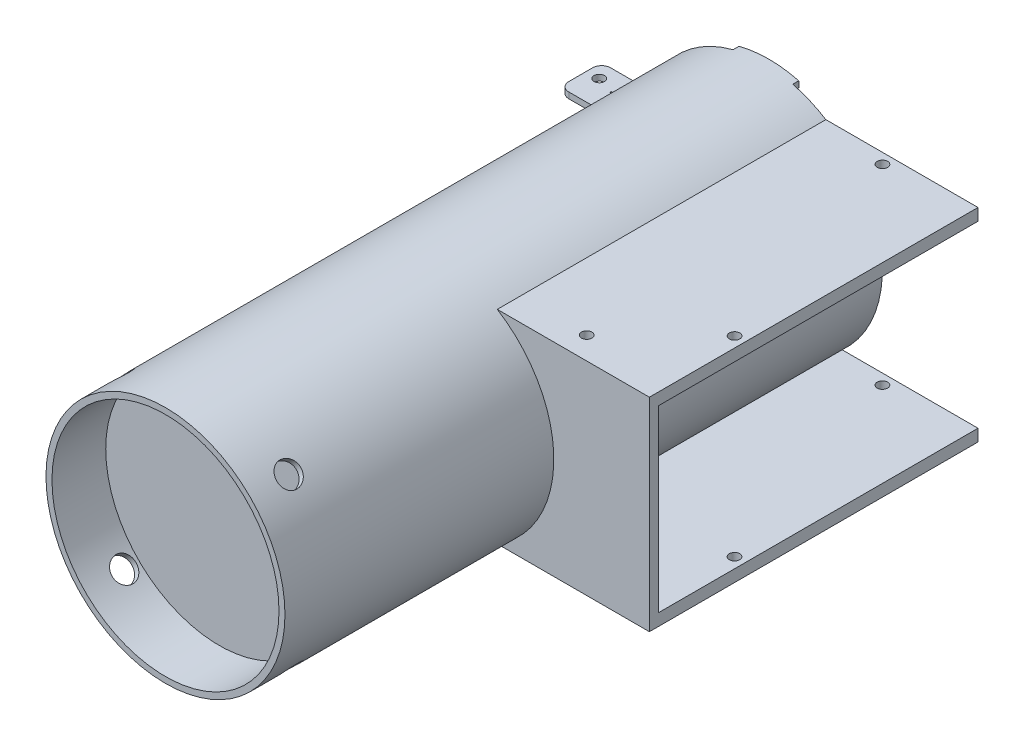
SolidWorks part; units mm, degrees
material "Acrylic (Medium-high impact)"
ref_plane "Front Plane" through (0, 0, 0) normal (0, 0, 1) x (1, 0, 0)
ref_plane "Top Plane" through (0, 0, 0) normal (0, 1, 0) x (1, 0, 0)
ref_plane "Right Plane" through (0, 0, 0) normal (1, 0, 0) x (0, 0, -1)
ref_axis "Axis1" through (0, 0, 106.8) along (0, 0, 1)
sketch "Sketch1" plane through (0, 0, 0) normal (0, 0, 1) x (1, 0, 0)
  circle A0 centre (0, 0) radius 38
  circle A1 centre (0, 0) radius 40
  dimension "D1" = 76
  dimension "D2" = 2
extrude "Boss-Extrude1" add sketch "Sketch1" along normal blind 200
ref_plane "Plane1" through (0, 0, 180) normal (0, 0, 1) x (1, 0, 0)
sketch "Sketch2" plane through (0, 0, 180) normal (0, 0, 1) x (1, 0, 0)
  circle A0 centre (0, 0) radius 40 construction
  circle A1 centre (0, 0) radius 40
extrude "Boss-Extrude2" add sketch "Sketch2" along normal blind 2
sketch "Sketch3" plane through (0, 0, 0) normal (0, 0, -1) x (-1, 0, 0)
  line L0 (-21.0713, -34) -> (-72, -34)
  line L1 (-72, -34) -> (-72, -30)
  line L2 (-72, -30) -> (-26.4575, -30)
  line L3 (-21.0713, 34) -> (-72, 34)
  line L4 (-72, 30) -> (-26.4575, 30)
  line L5 (-72, 34) -> (-72, 30)
  line L6 (-40, -15.2942) -> (-40, 13.2229) construction
  line L8 (0, 0) -> (-59.0266, 0) construction
  circle A1 centre (0, 0) radius 40 construction
  arc A2 (-21.0713, 34) -> (-26.4575, 30) centre (0, 0) ccw
  arc A3 (-26.4575, -30) -> (-21.0713, -34) centre (0, 0) ccw
  dimension "D1" = 60
  dimension "D2" = 4
  dimension "D3" = 32
extrude "Boss-Extrude3" add sketch "Sketch3" against normal blind 107
sketch "Sketch4" plane through (0, 0, 107) normal (0, 0, 1) x (1, 0, 0)
  line L2 (72, -34) -> (21.0713, -34) construction
  line L3 (21.0713, 34) -> (72, 34) construction
  line L4 (72, -34) -> (21.0713, -34)
  line L5 (21.0713, 34) -> (72, 34)
  line L6 (72, -34) -> (72, 34)
  circle A0 centre (0, 0) radius 40 construction
  arc A2 (21.0713, -34) -> (21.0713, 34) centre (0, 0) ccw
extrude "Boss-Extrude4" add sketch "Sketch4" along normal blind 3
sketch "Sketch5" plane through (0, 34, 0) normal (0, 1, 0) x (1, 0, 0)
  circle A5 centre (43.5, -102.5) radius 1.75 construction
  circle A6 centre (43.5, -102.5) radius 1.75
  circle A7 centre (43.5, -3.5) radius 1.75 construction
  circle A8 centre (43.5, -3.5) radius 1.75
  circle A9 centre (68.5, -78) radius 1.75 construction
  circle A10 centre (68.5, -78) radius 1.75
extrude "Cut-Extrude1" cut sketch "Sketch5" against normal through all
ref_plane "Plane2" through (0, 0, 0) normal (-0.7071, 0.7071, 0) x (0, 0, 1)
sketch "Sketch6" plane through (0, 0, 0) normal (-0.7071, 0.7071, 0) x (0, 0, 1)
  line L0 (200, -40) -> (200, 40) construction
  line L1 (200, -40) -> (200, 40) construction
  circle A0 centre (187, 0) radius 4
  dimension "D1" = 8
  dimension "D2" = 13
extrude "Cut-Extrude2" cut sketch "Sketch6" against normal up to next and the other way up to next
pattern_circular "CirPattern1" count 2 every 90 about axis through (0, 0, 106.8) along (0, 0, 1) of "Cut-Extrude2"
ref_plane "Plane3" through (-54, 0, 0) normal (1, 0, 0) x (0, 0, -1)
sketch "Sketch7" plane through (-54, 0, 0) normal (1, 0, 0) x (0, 0, -1)
  line L0 (0, 0) -> (-33.0452, 0) construction
  line L1 (-14, -11) -> (0, -11)
  line L2 (-14, -11) -> (-14, -13)
  line L3 (-14, -13) -> (0, -13)
  line L4 (0, -11) -> (0, -13)
  line L5 (0, -40) -> (0, 40) construction
  line L6 (0, 11) -> (0, 13)
  line L7 (-14, 13) -> (0, 13)
  line L8 (-14, 11) -> (-14, 13)
  line L9 (-14, 11) -> (0, 11)
  dimension "D1" = 2
  dimension "D2" = 14
  dimension "D3" = 22
extrude "Boss-Extrude5" add sketch "Sketch7" along normal up to surface (15.5422 mm away) up to face at (25.3934, 30.9059, 187.8976)
sketch "Sketch8" plane through (0, -13, 0) normal (0, -1, 0) x (1, 0, 0)
  line L6 (-37.8286, 14) -> (-37.8286, 0) construction
  line L7 (-37.8286, 0) -> (-54, 0) construction
  circle A0 centre (-49.7703, 5.0088) radius 1.75
  dimension "D3" = 3.5
  dimension "D1" = 11.9417
  dimension "D2" = 5.0088
extrude "Cut-Extrude3" cut sketch "Sketch8" against normal up to surface (26 mm away) up to face at (-45.9143, 13, 7)
fillet "Fillet1" radius 3 4 edges at (-54, 12, 0) (-54, -12, 0) (-54, -12, 14) (-54, 12, 14)
sketch "Sketch9" plane through (0, 11, 0) normal (0, -1, 0) x (1, 0, 0)
  circle A0 centre (-43.7703, 7.0088) radius 0.25
  circle A1 centre (-49.7703, 5.0088) radius 1.75 construction
  dimension "D1" = 6
  dimension "D2" = 2
  dimension "D3" = 0.5
extrude "Cut-Extrude4" cut sketch "Sketch9" against normal up to next
sketch "Sketch10" plane through (0, 0, 0) normal (0, 0, -1) x (-1, 0, 0)
  line L0 (-10, 38.7298) -> (-10, 36.6606)
  line L2 (10, 38.7298) -> (10, 36.6606)
  line L3 (-10, -36.6606) -> (-10, -38.7298)
  line L4 (10, -36.6606) -> (10, -38.7298)
  line L5 (-10, 36.6606) -> (10, 36.6606) construction
  line L6 (0, 36.6606) -> (0, 0) construction
  circle A0 centre (0, 0) radius 38 construction
  arc A1 (37.8286, 13) -> (-21.0713, 34) centre (0, 0) ccw construction
  arc A2 (-10, -36.6606) -> (10, -36.6606) centre (0, 0) ccw
  arc A3 (37.8286, 13) -> (-10, 38.7298) centre (0, 0) ccw
  arc A4 (10, 36.6606) -> (-10, 36.6606) centre (0, 0) ccw
  arc A5 (-21.0713, -34) -> (37.8286, -13) centre (0, 0) ccw construction
  arc A6 (-10, -38.7298) -> (37.8286, -13) centre (0, 0) ccw
  arc M9 (37.8286, 13) -> (-21.0713, 34) centre (0, 0) ccw
  arc M17 (-21.0713, -34) -> (37.8286, -13) centre (0, 0) ccw
  circle M22 centre (0, 0) radius 38
  dimension "D1" = 20
extrude "Boss-Extrude6" add sketch "Sketch10" along normal blind 2 contours L4 L3 M22 M17 | L2 L0 M9 M22 region at (0, 38.5641, 0) region at (0, -38.5641, 0)
sketch "Sketch11" plane through (0, 0, 200) normal (0, 0, 1) x (1, 0, 0)
  circle A0 centre (0, 0) radius 40 construction
  arc A1 (1.6429, -39.9662) -> (9.1587, 38.9374) centre (0, 0) ccw
  arc A2 (9.1587, 38.9374) -> (1.6429, -39.9662) centre (-30.2397, 2.8804) ccw
sketch "Sketch12" plane through (0, 0, 0) normal (0, 0, -1) x (-1, 0, 0)
  line L3 (-72, 30) -> (-26.4575, 30)
  line L4 (-21.0713, 34) -> (-72, 34)
  line L5 (-72, 34) -> (-72, 30)
  line L6 (-72, 30) -> (-26.4575, 30)
  line L7 (-21.0713, 34) -> (-72, 34)
  line L8 (-72, 34) -> (-72, 30)
  line L12 (-72, -34) -> (-21.0713, -34)
  line L13 (-26.4575, -30) -> (-72, -30)
  line L14 (-72, -30) -> (-72, -34)
  line L20 (-10, 36.6606) -> (-10, 38.7298)
  line L21 (-10, 36.6606) -> (-10, 38.7298)
  line L22 (-26.4575, -30) -> (-72, -30)
  line L23 (-26.4575, -30) -> (-72, -30)
  line L24 (-72, -30) -> (-72, -34)
  line L25 (-72, -30) -> (-72, -34)
  line L26 (-72, -34) -> (-21.0713, -34)
  line L27 (-72, -34) -> (-21.0713, -34)
  line L28 (-10, -38.7298) -> (-10, -36.6606)
  line L29 (-10, -38.7298) -> (-10, -36.6606)
  arc A1 (-10, 38.7298) -> (-21.0713, 34) centre (0, 0) ccw
  arc A2 (-10, 38.7298) -> (-21.0713, 34) centre (0, 0) ccw
  arc A4 (-26.4575, -30) -> (-21.0713, -34) centre (0, 0) ccw
  arc A8 (-26.4575, 30) -> (-26.4575, -30) centre (0, 0) ccw
  arc A9 (-26.4575, 30) -> (-26.4575, -30) centre (0, 0) ccw
  arc A10 (-21.0713, -34) -> (-10, -38.7298) centre (0, 0) ccw
  arc A11 (-21.0713, -34) -> (-10, -38.7298) centre (0, 0) ccw
  arc A12 (-10, 36.6606) -> (-10, -36.6606) centre (0, 0) ccw
  arc A13 (-10, 36.6606) -> (-10, -36.6606) centre (0, 0) ccw
  dimension "D1" = 0
